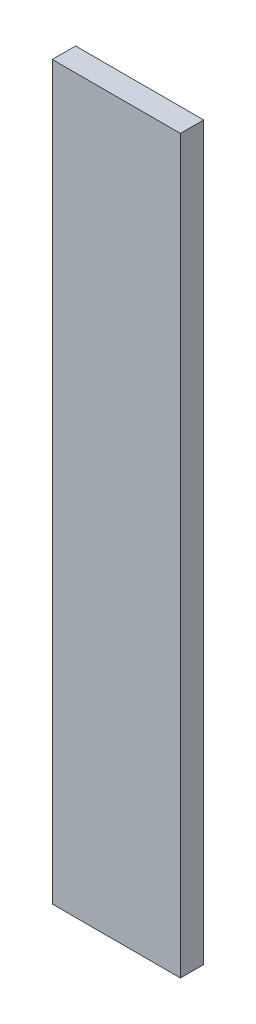
SolidWorks part; units mm, degrees
ref_plane "Front Plane" through (0, 0, 0) normal (0, 0, 1) x (1, 0, 0)
ref_plane "Top Plane" through (0, 0, 0) normal (0, 1, 0) x (1, 0, 0)
ref_plane "Right Plane" through (0, 0, 0) normal (1, 0, 0) x (0, 0, -1)
sketch "Sketch1" plane through (0, 0, 0) normal (0, 1, 0) x (1, 0, 0)
  line L1 (-19.5, 77.5) -> (19.5, 77.5)
  line L2 (-19.5, 77.5) -> (-19.5, -77.5)
  line L3 (-19.5, -77.5) -> (19.5, -77.5)
  line L4 (19.5, 77.5) -> (19.5, -77.5)
  line L5 (-19.5, 77.5) -> (19.5, -77.5) construction
  line L6 (-19.5, -77.5) -> (19.5, 77.5) construction
  point P0 (0, 0)
  dimension "D1" = 39
  dimension "D2" = 155
extrude "Boss-Extrude1" add sketch "Sketch1" along normal blind 2
sketch "Sketch2" plane through (0, 2, 0) normal (0, 1, 0) x (1, 0, 0)
  line L0 (-17.5, -75.5) -> (-17.5, -77.5)
  line L1 (-19.5, 77.5) -> (19.5, 77.5)
  line L2 (-19.5, 77.5) -> (-19.5, -77.5)
  line L3 (-19.5, -77.5) -> (19.5, -77.5)
  line L4 (19.5, 77.5) -> (19.5, -77.5)
  line L5 (-17.5, 75.5) -> (17.5, 75.5)
  line L6 (-17.5, 75.5) -> (-17.5, -75.5)
  line L7 (-17.5, -75.5) -> (17.5, -75.5)
  line L8 (17.5, 75.5) -> (17.5, -75.5)
  line L9 (-17.5, 75.5) -> (17.5, -75.5) construction
  line L10 (-17.5, -75.5) -> (17.5, 75.5) construction
  line L11 (17.5, -75.5) -> (17.5, -77.5)
  point P6 (0, 0)
  line M9 (19.5, -77.5) -> (19.5, 77.5)
  line M10 (19.5, 77.5) -> (-19.5, 77.5)
  line M11 (-19.5, 77.5) -> (-19.5, -77.5)
  line M12 (-19.5, -77.5) -> (19.5, -77.5)
  dimension "D1" = 2
  dimension "D2" = 2
extrude "Boss-Extrude2" add sketch "Sketch2" along normal blind 78 contours L8 L11 L3 L0 L6 L5 M9 M10 M11 M12 region at (-19.0983, 2, 76.5)
sketch "Sketch3" plane through (0, 2, 0) normal (0, 1, 0) x (1, 0, 0)
  line L0 (-17.5, 75.5) -> (-17.5, -77.5) construction
  line L1 (-17.5, -77.5) -> (-15.5, -77.5)
  line L2 (-17.5, -77.5) -> (-17.5, -75.5)
  line L3 (-17.5, -75.5) -> (-15.5, -75.5)
  line L4 (-15.5, -77.5) -> (-15.5, -75.5)
  line L5 (-17.5, -73.3) -> (-15.5, -73.3)
  line L6 (-17.5, -73.3) -> (-17.5, -71.3)
  line L7 (-17.5, -71.3) -> (-15.5, -71.3)
  line L8 (-15.5, -73.3) -> (-15.5, -71.3)
  line L9 (17.5, 75.5) -> (17.5, -77.5) construction
  line L10 (17.5, -77.5) -> (15.5, -77.5)
  line L11 (17.5, -77.5) -> (17.5, -75.5)
  line L12 (17.5, -75.5) -> (15.5, -75.5)
  line L13 (15.5, -77.5) -> (15.5, -75.5)
  line L14 (17.5, -73.3) -> (15.5, -73.3)
  line L15 (17.5, -73.3) -> (17.5, -71.3)
  line L16 (17.5, -71.3) -> (15.5, -71.3)
  line L17 (15.5, -73.3) -> (15.5, -71.3)
  line L18 (15.5, -75.5) -> (15.5, -73.3) construction
  line L19 (-15.5, -73.3) -> (15.5, -73.3) construction
  line L20 (-15.5, -75.5) -> (-15.5, -73.3) construction
  line L21 (-15.5, -75.5) -> (15.5, -75.5) construction
  line L22 (15.5, -71.3) -> (-15.5, -71.3) construction
  dimension "D1" = 2
  dimension "D2" = 2
  dimension "D3" = 2.2
  dimension "D4" = 2
extrude "Boss-Extrude3" add sketch "Sketch3" along normal up to surface (78 mm away) up to face at (0, 80, 0.5)
sketch "Sketch4" plane through (0, 0, -75.5) normal (0, 0, 1) x (1, 0, 0)
  line L0 (-17.5, 80) -> (-15.5, 80)
  line L1 (-17.5, 80) -> (17.5, 80) construction
  line L2 (-15.5, 80) -> (-15.5, 78)
  line L3 (-15.5, 78) -> (-17.5, 78)
  line L5 (-17.5, 78) -> (-17.5, 80)
  line L7 (-17.5, 80) -> (-17.5, 2) construction
  line L8 (-15.5, 73.8) -> (-17.5, 71.8)
  line L9 (-17.5, 71.8) -> (-17.5, 75.8)
  line L10 (-15.5, 73.8) -> (-15.5, 75.8)
  line L11 (-15.5, 75.8) -> (-17.5, 75.8)
  line L12 (0, 0) -> (0, 80) construction
  line L13 (15.5, 75.8) -> (17.5, 75.8)
  line L14 (15.5, 73.8) -> (15.5, 75.8)
  line L15 (17.5, 71.8) -> (17.5, 75.8)
  line L16 (15.5, 73.8) -> (17.5, 71.8)
  line L17 (17.5, 78) -> (17.5, 80)
  line L18 (15.5, 78) -> (17.5, 78)
  line L19 (15.5, 80) -> (15.5, 78)
  line L20 (17.5, 80) -> (15.5, 80)
  dimension "D1" = 2
  dimension "D2" = 2
  dimension "D3" = 45
  dimension "D4" = 2.2
  dimension "D5" = 2
extrude "Boss-Extrude4" add sketch "Sketch4" along normal up to surface (153 mm away) up to face at (0, 40.5, 77.5)
sketch "Sketch5" plane through (0, 2, 0) normal (0, 1, 0) x (1, 0, 0)
  line L1 (-15.5, -77.5) -> (15.5, -77.5)
  line L2 (-15.5, -77.5) -> (-15.5, -75.5)
  line L3 (-15.5, -75.5) -> (15.5, -75.5)
  line L4 (15.5, -77.5) -> (15.5, -75.5)
  line L5 (-15.5, -71.3) -> (15.5, -71.3)
  line L6 (-15.5, -71.3) -> (-15.5, -73.3)
  line L7 (-15.5, -73.3) -> (15.5, -73.3)
  line L8 (15.5, -71.3) -> (15.5, -73.3)
sketch "Sketch6" plane through (0, 0, -75.5) normal (0, 0, 1) x (1, 0, 0)
  line L0 (-17.5, 78) -> (-15.5, 78) construction
  line L1 (-17.5, 78) -> (17.5, 78)
  line L2 (-17.5, 78) -> (-17.5, 75.8)
  line L3 (-17.5, 75.8) -> (17.5, 75.8)
  line L4 (17.5, 78) -> (17.5, 75.8)
  line L5 (-17.5, 78) -> (-17.5, 75.8) construction
  line L6 (-15.5, 75.8) -> (-17.5, 75.8) construction
extrude "Cut-Extrude1" cut sketch "Sketch6" along normal through all
sketch "Sketch7" plane through (0, 2, 0) normal (0, 1, 0) x (1, 0, 0)
  line L1 (-17.5, -75.5) -> (17.5, -75.5)
  line L2 (-17.5, -75.5) -> (-17.5, -73.3)
  line L3 (-17.5, -73.3) -> (17.5, -73.3)
  line L4 (17.5, -75.5) -> (17.5, -73.3)
extrude "Cut-Extrude2" cut sketch "Sketch7" along normal through all
extrude "Boss-Extrude5" add sketch "Sketch5" along normal blind 2
sketch "Sketch8" plane through (0, 0, 0) normal (1, 0, 0) x (0, 0, -1)
  line L0 (75.5, 80) -> (73.5, 80)
  line L1 (-73.3, 80) -> (75.5, 80) construction
  line L2 (73.5, 80) -> (73.5, 78)
  line L3 (-73.3, 78) -> (75.5, 78) construction
  line L4 (73.5, 78) -> (75.5, 78)
  line L5 (75.5, 78) -> (75.5, 80)
  line L6 (75.5, 75.8) -> (73.5, 75.8)
  line L7 (-73.3, 75.8) -> (75.5, 75.8) construction
  line L8 (73.5, 75.8) -> (73.5, 73.8)
  line L9 (-71.3, 73.8) -> (75.5, 73.8) construction
  line L10 (73.5, 73.8) -> (75.5, 71.8)
  line L11 (75.5, 71.8) -> (75.5, 75.8)
  dimension "D1" = 2
extrude "Boss-Extrude6" add sketch "Sketch8" along normal up to surface and the other way up to surface up to face at (17.5, 36.9, -2.1) other way up to face at (-17.5, 36.9, -2.1)
sketch "Sketch10" plane through (-17.5, 0, 0) normal (1, 0, 0) x (0, 0, -1)
  line L1 (-75.5, 75.8) -> (-77.5, 75.8)
  line L2 (-75.5, 75.8) -> (-75.5, 78)
  line L3 (-75.5, 78) -> (-77.5, 78)
  line L4 (-77.5, 75.8) -> (-77.5, 78)
  line L5 (-73.3, 80) -> (-75.5, 80)
  line L6 (-73.3, 80) -> (-73.3, 78)
  line L7 (-73.3, 78) -> (-75.5, 78)
  line L8 (-75.5, 80) -> (-75.5, 78)
  line M1 (-75.5, 80) -> (-75.5, 78)
  line M2 (-75.5, 78) -> (-77.5, 78)
  line M3 (-77.5, 78) -> (-77.5, 75.8)
  line M4 (-77.5, 75.8) -> (-75.5, 75.8)
  line M11 (-73.3, 78) -> (-73.3, 80)
  line M12 (-73.3, 80) -> (-75.5, 80)
extrude "Boss-Extrude8" add sketch "Sketch10" along normal up to surface (2 mm away) contours L2 M4 M2 M3 | L7 M11 M12 M1 region at (-17.5, 79, 74.4) region at (-17.5, 76.9, 76.5) up to face at (-15.5, 79, -0.1)
sketch "Sketch11" plane through (17.5, 0, 0) normal (-1, 0, 0) x (0, 0, 1)
  line L1 (75.5, 75.8) -> (77.5, 75.8)
  line L2 (75.5, 75.8) -> (75.5, 78)
  line L3 (75.5, 78) -> (77.5, 78)
  line L4 (77.5, 75.8) -> (77.5, 78)
  line L5 (73.3, 80) -> (75.5, 80)
  line L6 (73.3, 80) -> (73.3, 78)
  line L7 (73.3, 78) -> (75.5, 78)
  line L8 (75.5, 80) -> (75.5, 78)
  line M2 (75.5, 75.8) -> (77.5, 75.8)
  line M3 (77.5, 75.8) -> (77.5, 78)
  line M4 (77.5, 78) -> (75.5, 78)
  line M5 (75.5, 78) -> (75.5, 80)
  line M6 (75.5, 80) -> (73.3, 80)
  line M7 (73.3, 80) -> (73.3, 78)
extrude "Boss-Extrude9" add sketch "Sketch11" along normal up to surface (2 mm away) contours L2 M2 M3 M4 | L7 M7 M5 M6 region at (17.5, 76.9, 76.5) region at (17.5, 79, 74.4) up to face at (15.5, 79, -0.1)
fillet "Fillet2" radius 2.5 17 edges at (-17.5, 36.9, 71.3) (17.5, 36.9, 71.3) (19.5, 40, 77.5) (-19.5, 40, 77.5) (-19.5, 40, -77.5) (-17.5, 36.9, -75.5) (17.5, 36.9, -75.5) (19.5, 40, -77.5) (-19.5, 80, 0) (0, 80, -77.5) (19.5, 80, 0) (0, 0, -77.5) (0, 0, 77.5) (-19.5, 0, 0) (19.5, 0, 0) (-17.5, 80, 77.5) (17.5, 80, 77.5)
sketch "Sketch13" plane through (0, 0, -77.5) normal (0, 0, -1) x (-1, 0, 0)
  line L0 (15.5, 77.5) -> (15.5, 4) construction
  line L1 (-15.5, 7) -> (15.5, 7)
  line L2 (-15.5, 7) -> (-15.5, 4)
  line L3 (-15.5, 4) -> (15.5, 4)
  line L4 (15.5, 7) -> (15.5, 4)
  dimension "D1" = 3
sketch "Sketch14" plane through (0, 0, -75.5) normal (0, 0, 1) x (1, 0, 0)
  line L1 (-18.25, 9) -> (18.25, 9)
  line L2 (-18.25, 9) -> (-18.25, 1.25)
  line L3 (-18.25, 1.25) -> (18.25, 1.25)
  line L4 (18.25, 9) -> (18.25, 1.25)
  line L5 (15.5, 7) -> (-15.5, 7) construction
  line L7 (17, 0) -> (17, 2.5) construction
  line L8 (19.5, 2.5) -> (17, 2.5) construction
  line L10 (-19.5, 2.5) -> (-17, 2.5) construction
  point P20 (17, 1.25)
  point P23 (18.25, 2.5)
  point P26 (-18.25, 2.5)
  dimension "D1" = 2
extrude "Boss-Extrude10" add sketch "Sketch14" along normal blind 2
extrude "Cut-Extrude4" cut sketch "Sketch13" against normal blind 2
fillet "Fillet3" radius 2 1 edges at (0, 9, -73.5)
fillet "Fillet4" radius 0.5 12 edges at (0, 4, -77.5) (0, 7, -77.5) (15.5, 7, -76.5) (15.5, 4, -76.5) (15.5, 5.5, -77.5) (-15.5, 4, -76.5) (-15.5, 7, -76.5) (-15.5, 5.5, -77.5) (0, 7, -75.5) (-15.5, 5.5, -75.5) (0, 4, -75.5) (15.5, 5.5, -75.5)
sketch "Sketch15" plane through (0, 0, 0) normal (0, -1, 0) x (1, 0, 0)
  line L0 (0, 77.5) -> (0, 0) construction
  line L1 (-17, 77.5) -> (17, 77.5) construction
  line L2 (0, 0) -> (0, -77.5) construction
  line L4 (17, -77.5) -> (-17, -77.5) construction
  circle A0 centre (0, 38.75) radius 5.1
  circle A1 centre (0, -38.75) radius 5.1
  dimension "D1" = 10.2
extrude "Cut-Extrude5" cut sketch "Sketch15" against normal through all
sketch "Sketch16" plane through (0, 2, 0) normal (0, 1, 0) x (1, 0, 0)
  circle A0 centre (0, 38.75) radius 7.1
  circle A1 centre (0, -38.75) radius 7.1
  circle A2 centre (0, 38.75) radius 5.1 construction
  dimension "D1" = 2
extrude "Boss-Extrude11" add sketch "Sketch16" along normal blind 1
fillet "Fillet5" radius 0.5 4 edges at (0, 2, 45.85) (0, 2, -31.65) (0, 3, 45.85) (0, 3, -31.65)
fillet "Fillet7" radius 0.5 8 edges at (15.5, 80, 0.75) (15.5, 79.2678, 76.7678) (-15.5, 80, 0.75) (-15.5, 79.2678, 76.7678) (0, 80, -73.5) (0, 4, 77.5) (15.5, 40.75, 77.5) (-15.5, 40.75, 77.5)
sketch "Sketch17" plane through (0, 0, 0) normal (0, 0, 1) x (1, 0, 0)
  line L0 (-16, 80) -> (16, 80) construction
  line L1 (-14.5, 80) -> (14.5, 80)
  line L2 (-14.5, 80) -> (-14.5, 9)
  line L3 (-14.5, 9) -> (14.5, 9)
  line L4 (14.5, 80) -> (14.5, 9)
  line L5 (15, 9) -> (-15, 9) construction
  line L6 (0, 0) -> (0, 9) construction
  line L8 (19.5, 77.5) -> (19.5, 2.5) construction
  line L9 (-19.5, 80) -> (19.5, 80)
  line L10 (-19.5, 80) -> (-19.5, 0)
  line L11 (-19.5, 0) -> (19.5, 0)
  line L12 (19.5, 80) -> (19.5, 0)
  line L13 (-19.5, 2.5) -> (-19.5, 77.5) construction
  line L14 (17, 0) -> (-17, 0) construction
  dimension "D1" = 29
extrude "Cut-Extrude7" cut sketch "Sketch17" against normal through all both and the other way through all contours L6 L11 L12 L9 L4 L3 | L11 L6 L3 L2 L9 L10 region at (-14.6016, 31.2672, 0) region at (14.6016, 31.2672, 0)
sketch "Sketch18" plane through (0, 0, 0) normal (0, 0, 1) x (1, 0, 0)
  line L0 (-14.5, 80) -> (14.5, 80) construction
  line L1 (14.5, 9) -> (-14.5, 9)
  line L2 (14.5, 9) -> (14.5, 80)
  line L3 (14.5, 80) -> (-14.5, 80)
  line L4 (-14.5, 9) -> (-14.5, 80)
  line L5 (14.5, 9) -> (-14.5, 80) construction
  line L6 (14.5, 80) -> (-14.5, 9) construction
  line L8 (-5.5, 80) -> (5.5, 80)
  line L9 (-5.5, 80) -> (-5.5, 9)
  line L10 (-5.5, 9) -> (5.5, 9)
  line L11 (5.5, 80) -> (5.5, 9)
  line L12 (-5.5, 80) -> (5.5, 9) construction
  line L13 (-5.5, 9) -> (5.5, 80) construction
  point P0 (0, 44.5)
  point P7 (0, 44.5)
  dimension "D1" = 11
extrude "Cut-Extrude8" cut sketch "Sketch18" against normal through all contours L3 L11 L1 L2 | L9 L3 L4 L1 region at (10, 44.5, 0) region at (-10, 44.5, 0)
sketch "Sketch19" plane through (0, 0, -75.5) normal (0, 0, 1) x (1, 0, 0)
  line L1 (-5.5, 80) -> (5.5, 80)
  line L2 (-5.5, 80) -> (-5.5, 71.8)
  line L3 (-5.5, 71.8) -> (5.5, 71.8)
  line L4 (5.5, 80) -> (5.5, 71.8)
extrude "Cut-Extrude9" cut sketch "Sketch19" against normal through all both and the other way through all
